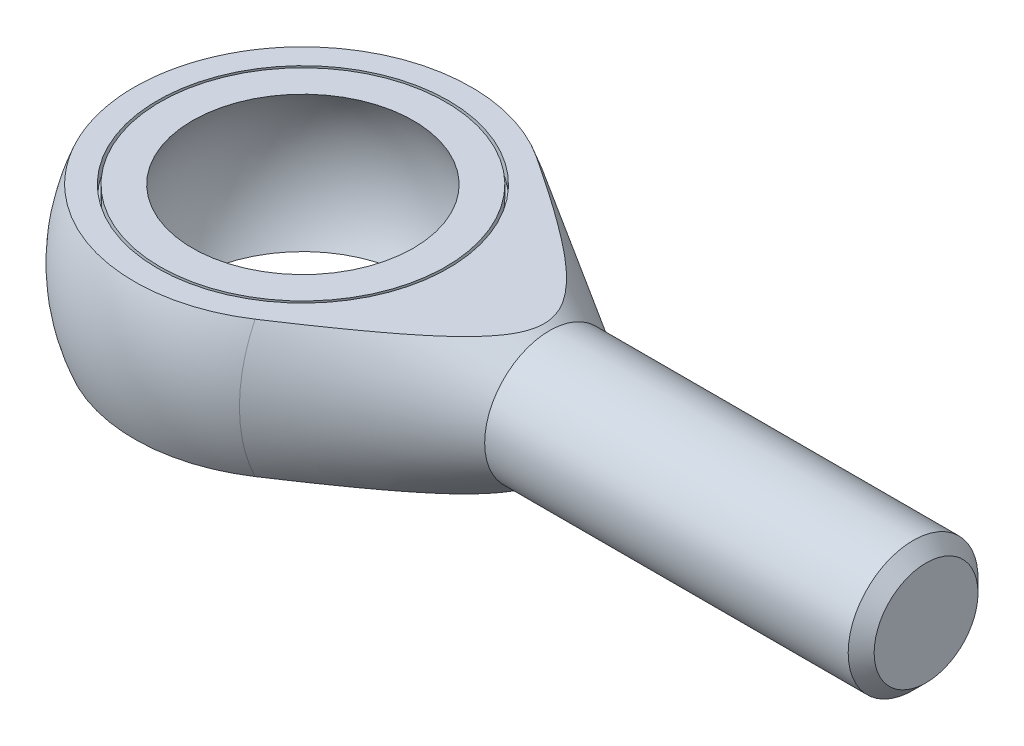
SolidWorks part; units mm, degrees
ref_plane "Front Plane" through (0, 0, 0) normal (0, 0, 1) x (1, 0, 0)
ref_plane "Top Plane" through (0, 0, 0) normal (0, 1, 0) x (1, 0, 0)
ref_plane "Right Plane" through (0, 0, 0) normal (1, 0, 0) x (0, 0, -1)
sketch "Sketch2" plane through (0, 0, 0) normal (0, 1, 0) x (1, 0, 0)
  line L0 (-39.4564, 0) -> (78.5867, 0) construction
  line L1 (7.148, 12.0377) -> (19, 5)
  line L2 (19, 5) -> (19, 0)
  line L3 (7.148, -12.0377) -> (19, -5) construction
  line L4 (-14, 0) -> (19, 0)
  arc A0 (-14, 0) -> (7.148, 12.0377) centre (0, 0) cw
  point P9 (19, 0)
  dimension "D2" = 14
  dimension "D1" = 10
  dimension "D3" = 19
revolve "Revolve2" add sketch "Sketch2" angle 360 about L0
sketch "Sketch3" plane through (0, 0, 0) normal (0, 0, 1) x (1, 0, 0)
  line L0 (-25.3278, 0) -> (34.1862, 0) construction
  line L1 (19, -5) -> (19, 5) construction
  line L2 (-14, 14) -> (19, 14)
  line L3 (-14, 14) -> (-14, 5.25)
  line L4 (-14, 5.25) -> (19, 5.25)
  line L5 (19, 14) -> (19, 5.25)
  line L6 (19, -14) -> (19, -5.25)
  line L7 (-14, -5.25) -> (19, -5.25)
  line L8 (-14, -14) -> (-14, -5.25)
  line L9 (-14, -14) -> (19, -14)
  arc A0 (7.148, 12.0377) -> (7.148, -12.0377) centre (0, 0) ccw construction
  dimension "D1" = 10.5
extrude "Cut-Extrude1" cut sketch "Sketch3" against normal through all and the other way through all
sketch "Sketch4" plane through (0, 0, 0) normal (0, 0, 1) x (1, 0, 0)
  line L0 (0, 13.976) -> (0, -14.0647) construction
  line L1 (0, 10) -> (0, -10)
  line L2 (-19.0477, 0) -> (26.0722, 0) construction
  line L3 (18.579, 5.25) -> (7.148, 5.25) construction
  line L4 (11, 5.25) -> (11.2, 5.25)
  line L5 (11, 5.25) -> (11, 4.25)
  line L6 (11, 4.25) -> (11.2, 4.25)
  line L7 (11.2, 5.25) -> (11.2, 4.25)
  line L8 (11.2, -5.25) -> (11.2, -4.25)
  line L9 (11, -4.25) -> (11.2, -4.25)
  line L10 (11, -5.25) -> (11, -4.25)
  line L11 (11, -5.25) -> (11.2, -5.25)
  arc A0 (0, -10) -> (0, 10) centre (0, 0) ccw
  dimension "D1" = 20
  dimension "D2" = 1
  dimension "D3" = 0.2
  dimension "D4" = 11
revolve "Cut-Revolve1" cut sketch "Sketch4" angle 360 about L0
sketch "Sketch5" plane through (19, 0, 0) normal (1, 0, 0) x (0, 0, -1)
  circle A1 centre (0, 0) radius 5
  circle A2 centre (0, 0) radius 5
  dimension "D1" = 0
extrude "Boss-Extrude1" add sketch "Sketch5" along normal blind 29
chamfer "Chamfer1" distance 1 angle 45 1 edges at (48, 0, -5)
ref_axis "Axis1" through (0, 5.775, 0) along (0, -1, 0)
